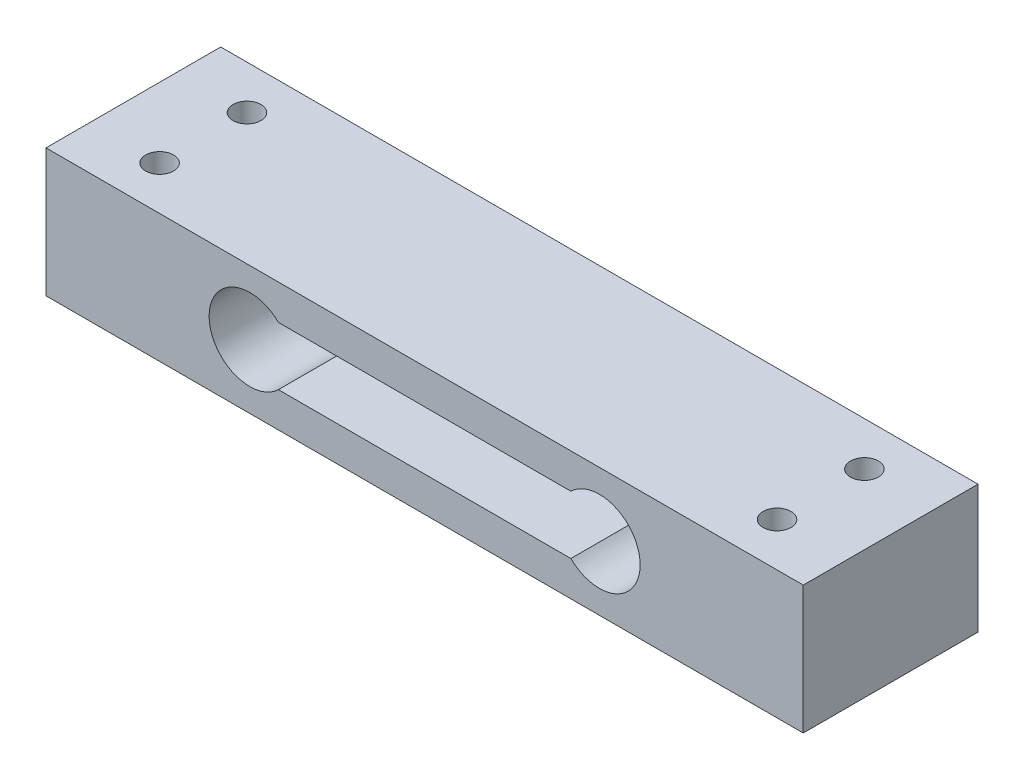
SolidWorks part; units mm, degrees
ref_plane "Ebene vorne" through (0, 0, 0) normal (0, 0, 1) x (1, 0, 0)
ref_plane "Ebene oben" through (0, 0, 0) normal (0, 1, 0) x (1, 0, 0)
ref_plane "Ebene rechts" through (0, 0, 0) normal (1, 0, 0) x (0, 0, -1)
sketch "Skizze2" plane through (0, 0, 0) normal (0, 1, 0) x (1, 0, 0)
  line L1 (-65, -15) -> (65, -15)
  line L2 (-65, -15) -> (-65, 15)
  line L3 (-65, 15) -> (65, 15)
  line L4 (65, -15) -> (65, 15)
  line L5 (-65, -15) -> (65, 15) construction
  line L6 (-65, 15) -> (65, -15) construction
  line L9 (0, -6.985) -> (0, 6.985) construction
  circle A2 centre (-53, -7.5) radius 2.4
  circle A3 centre (-53, 7.5) radius 2.4
  circle A4 centre (53, -7.5) radius 2.4
  circle A5 centre (53, 7.5) radius 2.4
  point P0 (0, 0)
  dimension "D3" = 30
  dimension "D4" = 12
  dimension "D5" = 15
  dimension "D1" = 12
  dimension "D6" = 4.8
  dimension "D7" = 4.8
  dimension "D2" = 130
extrude "Aufsatz-Linear austragen1" add sketch "Skizze2" along normal blind 11 and the other way blind 11
sketch "Skizze3" plane through (0, 0, 0) normal (0, 0, 1) x (1, 0, 0)
ref_plane "Ebene1" through (0, 0, 0) normal (0, 1, 0) x (1, 0, 0)
sketch "Skizze4" plane through (0, 0, 0) normal (0, 1, 0) x (1, 0, 0)
  line L4 (-37.5, -6.35) -> (37.5, -6.35)
  line L5 (-37.5, -6.35) -> (-37.5, 6.35)
  line L6 (-37.5, 6.35) -> (37.5, 6.35)
  line L7 (37.5, -6.35) -> (37.5, 6.35)
  line L8 (-37.5, -6.35) -> (37.5, 6.35) construction
  line L9 (-37.5, 6.35) -> (37.5, -6.35) construction
  circle A0 centre (22.5, 0) radius 1.65
  circle A1 centre (32.5, 0) radius 1.65
  circle A2 centre (-32.5, 0) radius 1.65
  circle A3 centre (-22.5, 0) radius 1.65
  point P8 (0, 0)
sketch "Skizze5" plane through (0, 0, 15) normal (0, 0, 1) x (1, 0, 0)
  line L0 (-37.5, 0) -> (37.5, 0) construction
  line L1 (0, 0) -> (0, 22.2384) construction
  line L2 (-25.101, 5) -> (25.101, 5)
  line L3 (-25.101, -5) -> (25.101, -5)
  line L4 (-37.5, 0) -> (37.5, 0) construction
  arc A0 (-25.101, 5) -> (-25.101, -5) centre (-30, 0) ccw
  arc A1 (25.101, 5) -> (25.101, -5) centre (30, 0) cw
  point P12 (0, -5)
  point P13 (0, 5)
  dimension "D3" = 7
  dimension "D1" = 5
  dimension "D2" = 5
  dimension "D4" = 30
extrude "Schnitt-Linear austragen1" cut sketch "Skizze5" against normal up to next
